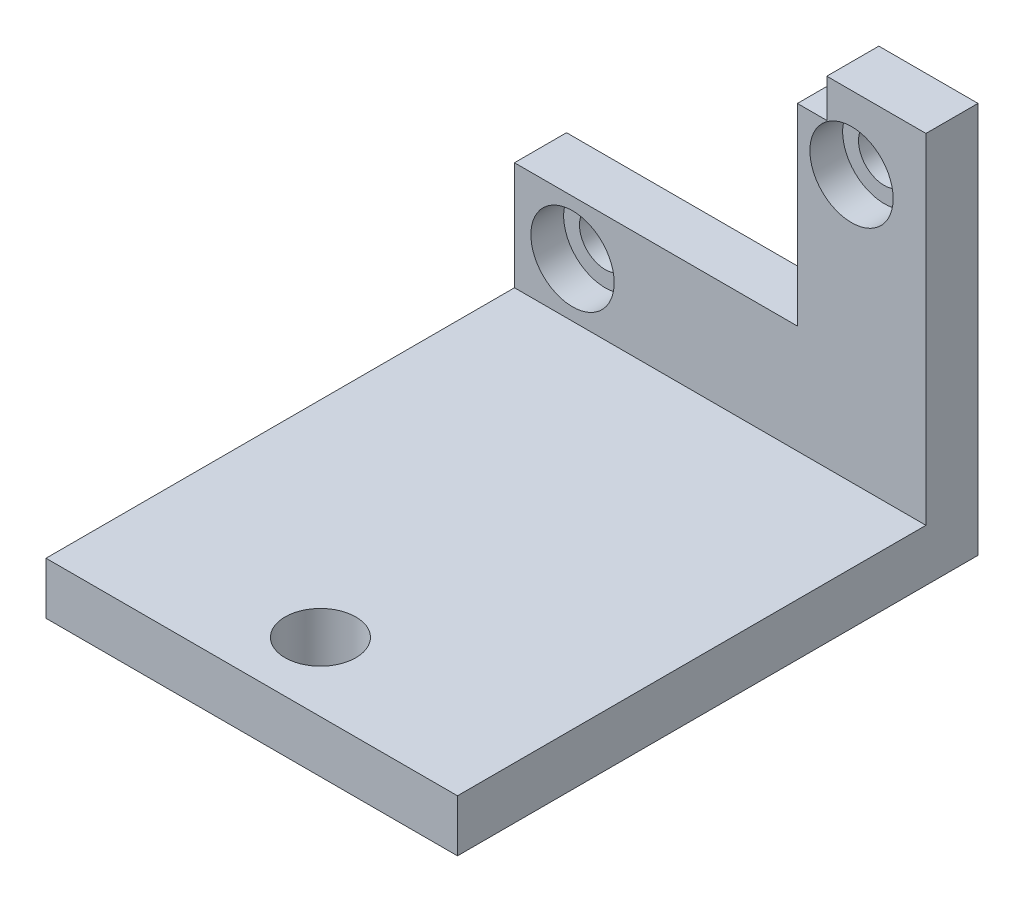
SolidWorks part; units mm, degrees
ref_plane "Front Plane" through (0, 0, 0) normal (0, 0, 1) x (1, 0, 0)
ref_plane "Top Plane" through (0, 0, 0) normal (0, 1, 0) x (1, 0, 0)
ref_plane "Right Plane" through (0, 0, 0) normal (1, 0, 0) x (0, 0, -1)
sketch "Sketch2" plane through (0, 0, 0) normal (0, 0, 1) x (1, 0, 0)
  line L0 (4.3952, 7.8274) -> (4.3952, -1.4384)
  line L1 (4.3952, -1.4384) -> (-11.8608, -1.4384)
  line L2 (-11.8608, -1.4384) -> (-11.8608, -8.0424)
  line L3 (-11.8608, -8.0424) -> (12.2372, -8.0424)
  line L4 (12.2372, -8.0424) -> (12.2372, 12.6586)
  line L5 (12.2372, 12.6586) -> (7.6972, 12.6586)
  line L7 (7.6972, 12.6586) -> (6.1882, 12.6586)
  line L8 (-11.8608, -1.4384) -> (-12.8608, -1.4384)
  line L9 (-11.8608, -1.4384) -> (-11.8608, -8.0424)
  line L10 (-11.8608, -8.0424) -> (-12.8608, -8.0424)
  line L11 (-12.8608, -1.4384) -> (-12.8608, -8.0424)
  line L12 (4.3952, 10.3218) -> (4.3952, 7.8274)
  line L13 (4.3952, 10.3218) -> (6.1882, 10.3218)
  line L14 (6.1882, 10.3218) -> (6.1882, 12.6586)
  circle A0 centre (7.6972, 8.2136) radius 1.5748
  circle A1 centre (-9.3208, -4.7404) radius 1.5748
  point P0 (6.4597, 9.1875)
  dimension "D5" = 4.445
  dimension "D7" = 3.1496
  dimension "D9" = 3.1496
  dimension "D1" = 1
  dimension "D2" = 3.302
  dimension "D3" = 3.302
  dimension "D4" = 24.098
  dimension "D6" = 2.54
  dimension "D8" = 17.018
  dimension "D10" = 14.097
extrude "Boss-Extrude1" add sketch "Sketch2" along normal blind 3.175 contours A0 | L8 L11 L10 L2 | L3 L4 L5 L7 L14 L13 L12 L0 L1 L2 | A1 region at (-12.3608, -4.7404, 0) region at (7.6972, 8.2136, 0)
sketch "Sketch3" plane through (0, 0, 0) normal (0, 0, -1) x (-1, 0, 0)
  line L6 (-12.2372, -8.0424) -> (12.8608, -8.0424)
  line L7 (-12.2372, -8.0424) -> (-12.2372, -11.2174)
  line L8 (-12.2372, -11.2174) -> (12.8608, -11.2174)
  line L9 (12.8608, -8.0424) -> (12.8608, -11.2174)
  dimension "D1" = 3.175
extrude "Boss-Extrude3" add sketch "Sketch3" against normal blind 31.75
sketch "Sketch4" plane through (0, -11.2174, 0) normal (0, -1, 0) x (1, 0, 0)
  line L0 (12.2372, 0) -> (-12.8608, 0) construction
  line L1 (-0.3118, 31.75) -> (-0.3118, 3.0754) construction
  line L2 (12.2372, 31.75) -> (-12.8608, 31.75) construction
  circle A0 centre (-0.3118, 27.559) radius 2.159
  dimension "D1" = 4.318
  dimension "D2" = 27.559
extrude "Cut-Extrude1" cut sketch "Sketch4" against normal through all
sketch "Sketch5" plane through (0, 0, 3.175) normal (0, 0, 1) x (1, 0, 0)
  circle A0 centre (7.6972, 8.2136) radius 2.54
  circle A1 centre (-9.3208, -4.7404) radius 2.54
  dimension "D1" = 5.08
  dimension "D2" = 5.08
extrude "Cut-Extrude2" cut sketch "Sketch5" against normal blind 2
